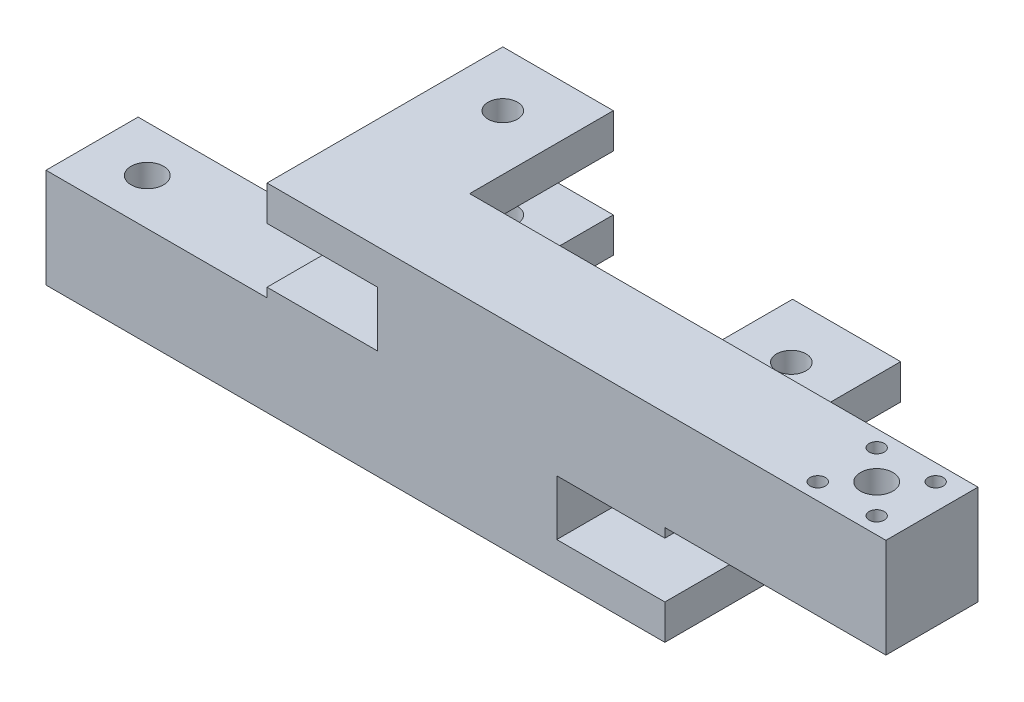
SolidWorks part; units mm, degrees
material "Ductile Iron"
ref_plane "Front Plane" through (0, 0, 0) normal (0, 0, 1) x (1, 0, 0)
ref_plane "Top Plane" through (0, 0, 0) normal (0, 1, 0) x (1, 0, 0)
ref_plane "Right Plane" through (0, 0, 0) normal (1, 0, 0) x (0, 0, -1)
sketch "Sketch1" plane through (0, 0, 0) normal (0, 0, 1) x (1, 0, 0)
  line L0 (-54, 27) -> (54, 27)
  line L5 (54, 27) -> (54, -2.5)
  line L6 (54, -2.5) -> (24.6547, -2.5)
  line L7 (24.6547, -2.5) -> (24.6547, -17.5)
  line L8 (24.6547, -17.5) -> (54, -17.5)
  line L9 (54, -17.5) -> (54, -27)
  line L10 (54, -27) -> (-54, -27)
  line L11 (-54, -27) -> (-54, 2.5)
  line L12 (-54, 2.5) -> (-24, 2.5)
  line L13 (-24, 2.5) -> (-24, 17.5)
  line L14 (-24, 17.5) -> (-54, 17.5)
  line L15 (-54, 17.5) -> (-54, 27)
  line L17 (-39, 17.5) -> (-39, 2.5) construction
  point P17 (0, 27)
  point P18 (0, -27)
  dimension "D5" = 15
  dimension "D1" = 30
  dimension "D2" = 39
  dimension "D6" = 15
  dimension "D3" = 5
  dimension "D4" = 2.5
  dimension "D7" = 9.5
  dimension "D8" = 9.5
extrude "Boss-Extrude1" add sketch "Sketch1" along normal blind 25
sketch "Sketch4" plane through (0, 0, 0) normal (0, 0, -1) x (-1, 0, 0)
  line L0 (-54, -2.5) -> (-54, 27) construction
  line L1 (-54, 7) -> (-24.6547, 7)
  line L2 (-54, 7) -> (-54, -2.5)
  line L3 (-54, -2.5) -> (-24.6547, -2.5)
  line L4 (-24.6547, 7) -> (-24.6547, -2.5)
  line L5 (-54, -17.5) -> (-24.6547, -17.5)
  line L6 (-54, -17.5) -> (-54, -27)
  line L7 (-54, -27) -> (-24.6547, -27)
  line L8 (-24.6547, -17.5) -> (-24.6547, -27)
  line L9 (-54, 27) -> (54, 27) construction
  line L10 (24, 2.5) -> (54, 2.5)
  line L11 (24, 2.5) -> (24, -7)
  line L12 (24, -7) -> (54, -7)
  line L13 (54, 2.5) -> (54, -7)
  line L14 (54, 17.5) -> (24, 17.5)
  line L15 (54, 17.5) -> (54, 27)
  line L16 (54, 27) -> (24, 27)
  line L17 (24, 17.5) -> (24, 27)
  line L19 (54, -27) -> (-54, -27) construction
extrude "Boss-Extrude2" add sketch "Sketch4" along normal blind 39
sketch "Sketch2" plane through (0, 27, 0) normal (0, 1, 0) x (1, 0, 0)
  line L0 (-39, 24) -> (39.3273, 24) construction
  line L1 (-39, 24) -> (-39, 39) construction
  line L2 (24.6547, 39) -> (54, 39) construction
  line L3 (-54, 39) -> (-24, 39) construction
  line L4 (39.3273, 24) -> (39.3273, 39) construction
  circle A1 centre (39.3273, 24) radius 4
  circle A2 centre (-39, 24) radius 4
  dimension "D3" = 8
  dimension "D1" = 15
extrude "Actuator Shaft Passthrough" cut sketch "Sketch2" against normal offset from surface (54.5 mm away) 10 up to face at (36.3928, -17.5, -5.6) offset beyond the face yes
sketch "Sketch6" plane through (54, 0, 0) normal (1, 0, 0) x (0, 0, -1)
  line L1 (-25, 27) -> (0, 27)
  line L2 (-25, 27) -> (-25, 0)
  line L3 (-25, 0) -> (0, 0)
  line L4 (0, 27) -> (0, 0)
  line L5 (-25, 27) -> (0, 0) construction
  line L6 (-25, 0) -> (0, 27) construction
  point P4 (-12.5, 13.5)
extrude "Boss-Extrude3" add sketch "Sketch6" along normal blind 60 contours L4 L3 L2 L1
sketch "Sketch7" plane through (-54, 0, 0) normal (-1, 0, 0) x (0, 0, 1)
  line L1 (25, -27) -> (0, -27)
  line L2 (25, -27) -> (25, 0)
  line L3 (25, 0) -> (0, 0)
  line L4 (0, -27) -> (0, 0)
  line L5 (25, -27) -> (0, 0) construction
  line L6 (25, 0) -> (0, -27) construction
  point P4 (12.5, -13.5)
extrude "Boss-Extrude4" add sketch "Sketch7" along normal blind 60
sketch "Sketch8" plane through (0, 0, 0) normal (0, 1, 0) x (1, 0, 0)
  line L0 (-114, -12.5) -> (99, -12.5) construction
  line L1 (-114, -25) -> (-114, 0) construction
  line L2 (114, -25) -> (114, 0) construction
  circle A0 centre (-99, -12.5) radius 4.4
  circle A1 centre (99, -12.5) radius 4.4
  dimension "D1" = 8.8
  dimension "D2" = 15
  dimension "D3" = 15
extrude "Cut-Extrude1" cut sketch "Sketch8" against normal through all both and the other way through all
sketch "Sketch9" plane through (0, 27, 0) normal (0, 1, 0) x (1, 0, 0)
  line L1 (91, -20.5) -> (107, -20.5) construction
  line L2 (91, -20.5) -> (91, -4.5) construction
  line L3 (91, -4.5) -> (107, -4.5) construction
  line L4 (107, -20.5) -> (107, -4.5) construction
  line L5 (91, -20.5) -> (107, -4.5) construction
  line L6 (91, -4.5) -> (107, -20.5) construction
  circle A0 centre (107, -4.5) radius 2.05
  circle A1 centre (91, -4.5) radius 2.05
  circle A2 centre (91, -20.5) radius 2.05
  circle A3 centre (107, -20.5) radius 2.05
  point P0 (99, -12.5)
  dimension "D3" = 4.1
  dimension "D1" = 16
  dimension "D2" = 16
extrude "Cut-Extrude2" cut sketch "Sketch9" against normal blind 10
equation "\"D4@Sketch1\"=\"D3@Sketch1\"/2"
